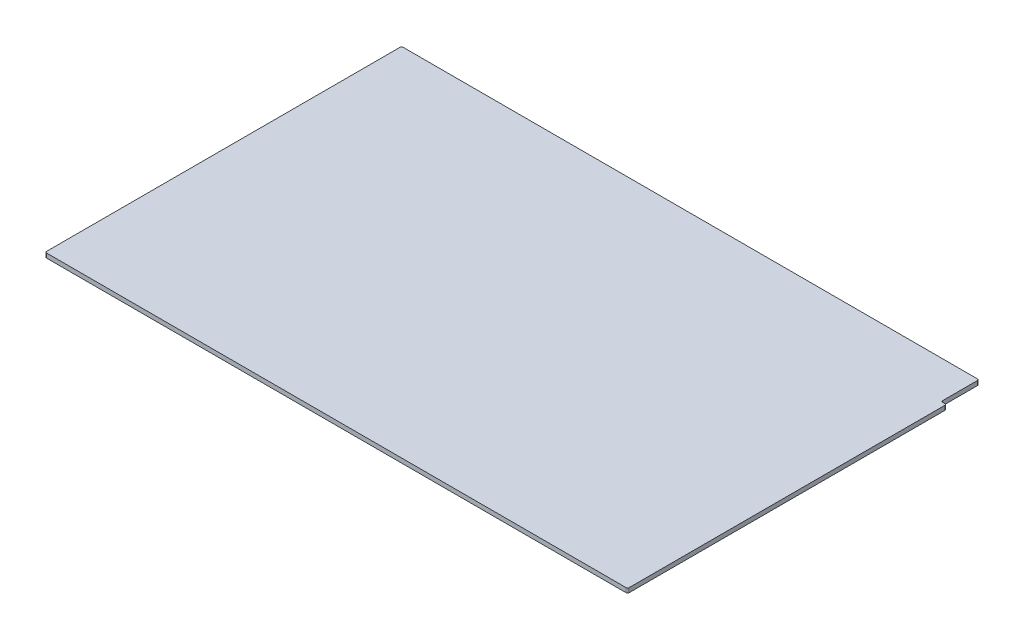
SolidWorks part; units mm, degrees
material "Plain Carbon Steel"
ref_plane "Front" through (0, 0, 0) normal (0, 0, 1) x (1, 0, 0)
ref_plane "Top" through (0, 0, 0) normal (0, 1, 0) x (1, 0, 0)
ref_plane "Right" through (0, 0, 0) normal (1, 0, 0) x (0, 0, -1)
sketch "Sketch1" plane through (0, 0, 0) normal (0, 1, 0) x (1, 0, 0)
  line L0 (0, 0) -> (0, 96.012)
  line L1 (0, 96.012) -> (156.8958, 96.012)
  line L2 (156.8958, 96.012) -> (156.8958, 0)
  line L4 (156.8958, 0) -> (0, 0)
  point P4 (156.8958, 0)
  dimension "D1" = 156.8958
  dimension "D2" = 96.012
base flange "Base-Flange1" sketch "Sketch1" thickness 1.1938 reverse thickness direction no parameters "D1"=1.4986
sketch "Sketch6" plane through (0, 0, 0) normal (0, 1, 0) x (1, 0, 0)
  line L0 (156.8958, 96.012) -> (0, 96.012) construction
  line L1 (156.8958, 96.012) -> (155.4988, 96.012)
  line L2 (156.8958, 96.012) -> (156.8958, 85.852)
  line L3 (156.8958, 85.852) -> (155.4988, 85.852)
  line L4 (155.4988, 96.012) -> (155.4988, 85.852)
  line L5 (156.8958, 0) -> (156.8958, 96.012) construction
  dimension "D1" = 1.397
  dimension "D2" = 10.16
extrude "Cut-Extrude1" cut sketch "Sketch6" against normal through all normal cut yes
fillet "Fillet1" radius 0.3969 6 edges at (156.8958, -0.5969, -85.852) (155.4988, -0.5969, -85.852) (155.4988, -0.5969, -96.012) (0, -0.5969, -96.012) (0, -0.5969, 0) (156.8958, -0.5969, 0)
sketch "Bend-Lines1" [suppressed] plane through (0, 0, 0) normal (0, 1, 0) x (1, 0, 0)
sketch "Bounding-Box1" [suppressed] plane through (0, 0, 0) normal (0, 1, 0) x (1, 0, 0)
sheet metal parameters "Sheet-Metal28" thickness 1.1938 parameters "D1"=2.4892
flat pattern "Flat-Pattern28" [suppressed]
sketch "Bend-Lines2" plane through (0, 0, 0) normal (0, 1, 0) x (1, 0, 0)
sketch3d "Bounding-Box2" [suppressed]
  line L0 (215.9, 96.012, 0) -> (0, 96.012, 0) construction
  line L1 (215.9, 0, 0) -> (0, 0, 0) construction
  line L2 (215.9, 96.012, 0) -> (215.9, 0, 0) construction
  line L3 (0, 96.012, 0) -> (0, 0, 0) construction
sheet metal parameters "Sheet-Metal29" thickness 1.1938 parameters "D1"=2.4892
flat pattern "Flat-Pattern28"
sketch "Bend-Lines2" plane through (0, 0, 0) normal (0, 1, 0) x (1, 0, 0)
sketch3d "Bounding-Box2" [suppressed]
  line L0 (156.8958, 96.012, 0) -> (0, 96.012, 0) construction
  line L1 (156.8958, 0, 0) -> (0, 0, 0) construction
  line L2 (156.8958, 96.012, 0) -> (156.8958, 0, 0) construction
  line L3 (0, 96.012, 0) -> (0, 0, 0) construction
equation "\"Total Cutting Length\"= \"Cutting Length-Outer\" + \"Cutting Length-Inner\""
equation "\"Amount in ft^2\"= \"Bounding Box Area-Blank\" / 144"
